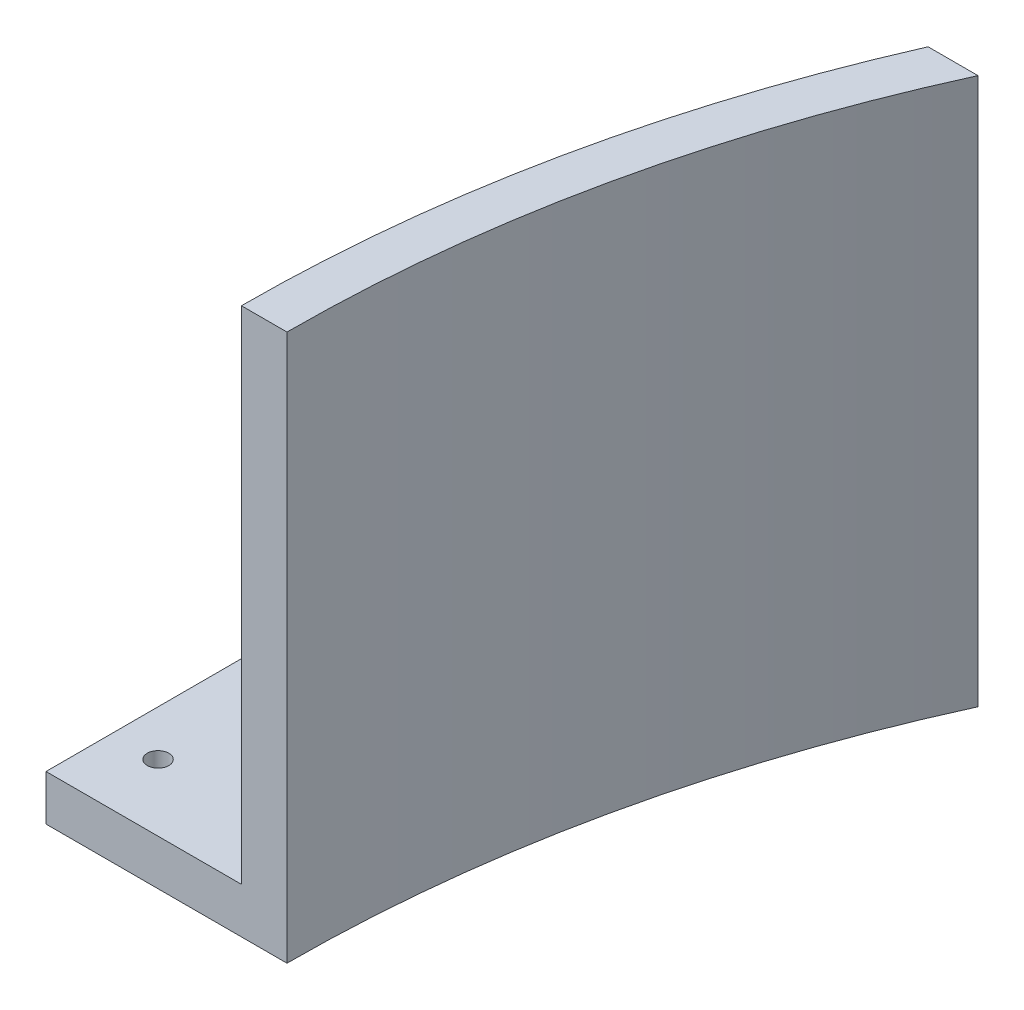
SolidWorks part; units mm, degrees
ref_plane "Front Plane" through (0, 0, 0) normal (0, 0, 1) x (1, 0, 0)
ref_plane "Top Plane" through (0, 0, 0) normal (0, 1, 0) x (1, 0, 0)
ref_plane "Right Plane" through (0, 0, 0) normal (1, 0, 0) x (0, 0, -1)
sketch "Sketch1" plane through (0, 0, 0) normal (0, 1, 0) x (1, 0, 0)
  line L0 (50.8, 79.121) -> (0, 79.121)
  line L1 (0, 79.121) -> (0, 0)
  line L2 (0, 0) -> (33.592, 0)
  arc A1 (50.8, 79.121) -> (33.592, 0) centre (224.092, 0) ccw
  dimension "D2" = 381
  dimension "D1" = 50.8
  dimension "D3" = 79.121
extrude "Boss-Extrude1" add sketch "Sketch1" along normal blind 76.2
sketch "Sketch3" plane through (0, 0, 0) normal (0, 1, 0) x (1, 0, 0)
  line L0 (27.242, 0) -> (0, 0)
  line L2 (0, 0) -> (0, 79.121)
  line L3 (0, 79.121) -> (43.8428, 79.121)
  line L5 (50.8, 79.121) -> (0, 79.121) construction
  arc A3 (45.0236, 81.7584) -> (27.242, 0) centre (224.092, 0) ccw
  arc A4 (43.8428, 79.121) -> (27.242, 0) centre (224.092, 0) ccw
  dimension "D1" = 6.35
extrude "Cut-Extrude1" cut sketch "Sketch3" against normal offset from surface (69.85 mm away) 6.35 from surface up to face at (20.0349, 0, -39.7917) starting at face at (20.0349, 76.2, -39.7917)
sketch "Sketch4" plane through (0, 6.35, 0) normal (0, 1, 0) x (1, 0, 0)
  line L0 (43.8428, 79.121) -> (0, 79.121) construction
  line L1 (0, 79.121) -> (0, 0) construction
  circle A0 centre (6.35, 72.771) radius 1.5
  circle A1 centre (25.4, 72.771) radius 1.5
  circle A3 centre (6.35, 9.271) radius 1.5
  circle A4 centre (25.4, 9.271) radius 1.5 [skipped]
  dimension "D1" = 3
  dimension "D2" = 6.35
  dimension "D3" = 6.35
  dimension "D4" = 2
  dimension "D5" = 2
extrude "Cut-Extrude2" cut sketch "Sketch4" against normal through all
equation "\"tightTol\" = 0.005in"
equation "\"normTol\"= 0.01in"
equation "\"looseTol\"= 0.02in"
equation "\"D3@Sketch1\"=3.125000in-\"normTol\""
equation "\"D1@Sketch4\"=3mm"
